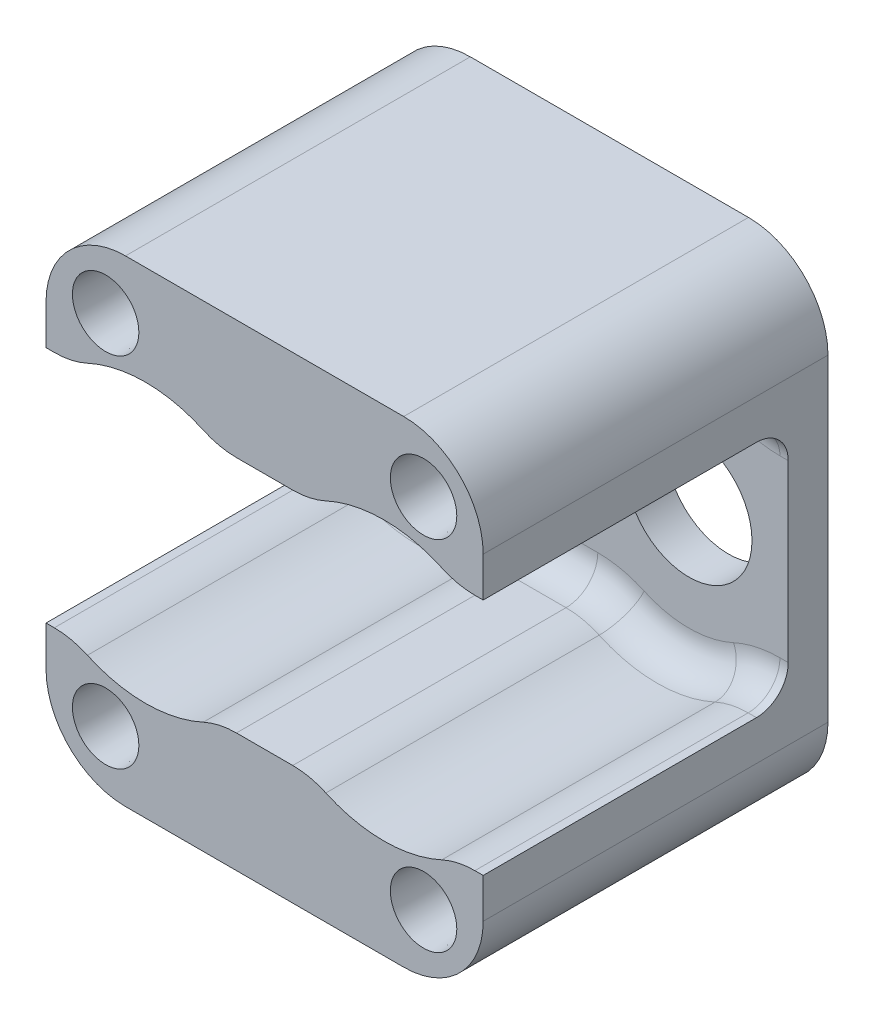
SolidWorks part; units mm, degrees
material "PET"
ref_plane "Front Plane" through (0, 0, 0) normal (0, 0, 1) x (1, 0, 0)
ref_plane "Top Plane" through (0, 0, 0) normal (0, 1, 0) x (1, 0, 0)
ref_plane "Right Plane" through (0, 0, 0) normal (1, 0, 0) x (0, 0, -1)
sketch "Sketch1" plane through (0, 0, 0) normal (0, 0, 1) x (1, 0, 0)
  line L0 (-19.05, 0) -> (0, 0) construction
  line L2 (7.9375, -19.05) -> (-26.9875, -19.05)
  line L3 (7.9375, -19.05) -> (7.9375, 19.05)
  line L4 (7.9375, 19.05) -> (-26.9875, 19.05)
  line L5 (-26.9875, -19.05) -> (-26.9875, 19.05)
  line L6 (7.9375, -19.05) -> (-26.9875, 19.05) construction
  line L7 (7.9375, 19.05) -> (-26.9875, -19.05) construction
  point P4 (-9.525, 0)
  dimension "D1" = 34.925
  dimension "D2" = 38.1
extrude "Boss-Extrude1" add sketch "Sketch1" along normal blind 3.175
sketch "Sketch2" plane through (0, 0, 3.175) normal (0, 0, 1) x (1, 0, 0)
  line L0 (7.9375, -19.05) -> (7.9375, 19.05) construction
  line L1 (-26.9875, 19.05) -> (7.9375, 19.05)
  line L2 (-26.9875, 19.05) -> (-26.9875, 9.525)
  line L3 (-26.9875, 9.525) -> (7.9375, 9.525)
  line L4 (7.9375, 19.05) -> (7.9375, 9.525)
  dimension "D1" = 9.525
extrude "Boss-Extrude2" add sketch "Sketch2" along normal up to surface (24.3713 mm away)
sketch "Sketch3" plane through (0, 0, 19.6088) normal (0, 0, 1) x (1, 0, 0)
  circle A0 centre (-19.05, 0) radius 11.1125
  circle A1 centre (0, 0) radius 11.1125
  dimension "D1" = 22.225
extrude "Cut-Extrude1" cut sketch "Sketch3" against normal up to surface (16.4338 mm away) and the other way through all contours A1 A0 | A0 A1 | A0 A1 region at (-9.525, 0, 19.6088) region at (0.6449, 0, 19.6088) region at (-19.6949, 0, 19.6088) up to face at (-13.8906, -4.7625, 3.175)
mirror "Mirror1" about plane through (0, 0, 0) normal (0, 1, 0) of "Cut-Extrude1", "Boss-Extrude2"
fillet "Fillet1" radius 6.35 12 edges at (7.9375, 19.05, 13.7732) (-26.9875, 19.05, 13.7732) (5.7238, 9.525, 15.3607) (-5.7238, 9.525, 15.3607) (-13.3262, 9.525, 15.3607) (-24.7738, 9.525, 15.3607) (7.9375, -19.05, 13.7732) (-26.9875, -19.05, 13.7732) (5.7238, -9.525, 15.3607) (-5.7238, -9.525, 15.3607) (-13.3262, -9.525, 15.3607) (-24.7738, -9.525, 15.3607)
fillet "Fillet2" radius 2.54 18 edges at (5.921, 9.671, 3.175) (0, 11.1125, 3.175) (-5.921, 9.671, 3.175) (-13.129, 9.671, 3.175) (-19.05, 11.1125, 3.175) (-24.971, 9.671, 3.175) (7.6062, -9.525, 3.175) (5.921, -9.671, 3.175) (0, -11.1125, 3.175) (-5.921, -9.671, 3.175) (-9.525, -9.525, 3.175) (-13.129, -9.671, 3.175) (-19.05, -11.1125, 3.175) (-24.971, -9.671, 3.175) (-26.6562, -9.525, 3.175)
sketch "Sketch4" plane through (0, 0, 3.175) normal (0, 0, 1) x (1, 0, 0)
  line L0 (-10.9857, 8.0643) -> (-27.1143, -8.0643) construction
  line L2 (-26.2611, -8.9174) -> (-27.9674, -7.2111) construction
  circle A0 centre (-19.05, 0) radius 4.9022
  point P8 (-19.05, 0)
  point P10 (-19.05, 0)
  dimension "D1" = 9.8044
extrude "Cut-Extrude2" cut sketch "Sketch4" against normal through all
hole_wizard "3/8 Clearance Hole1" positions "Sketch6" profile "Sketch5" hole size "3/8" standard "ANSI Inch" end condition through all
sketch "Sketch6" plane through (0, 0, 3.175) normal (0, 0, 1) x (1, 0, 0)
  point P0 (0, 0)
sketch "Sketch5" plane through (0, 0, 3.175) normal (1, 0, 0) x (0, -1, 0)
  line L0 (0, 0) -> (0, 3.175)
  line L1 (0, 3.175) -> (5.0419, 3.175)
  line L2 (5.0419, 3.175) -> (5.0419, 0)
  line L5 (5.0419, 0) -> (0, 0)
  line L11 (0, -6.35) -> (0, 107.95) construction
  dimension "Thru Hole Dia." = 10.0838
  dimension "Thru Hole Depth" = 3.175
hole_wizard "#6 Clearance Hole1" positions "Sketch8" profile "Sketch7" hole size "#6" standard "ANSI Inch" end condition through all
sketch "Sketch8" plane through (0, 0, 0) normal (0, 0, -1) x (-1, 0, 0)
  line L0 (-7.9375, -12.7) -> (-7.9375, 12.7) construction
  line L1 (-1.5875, 19.05) -> (20.6375, 19.05) construction
  line L2 (9.525, 19.05) -> (9.525, 0) construction
  line L3 (9.525, 0) -> (26.9875, 0) construction
  line L4 (26.9875, 12.7) -> (26.9875, -12.7) construction
  point P0 (-3.175, 14.2875)
  point P21 (22.225, 14.2875)
  point P23 (22.225, -14.2875)
  point P24 (-3.175, -14.2875)
  dimension "D1" = 4.7625
  dimension "D2" = 4.7625
sketch "Sketch7" plane through (3.175, 14.2875, 0) normal (1, 0, 0) x (0, 1, 0)
  line L0 (0, 0) -> (0, 27.5463)
  line L1 (0, 27.5463) -> (2.1526, 27.5463)
  line L2 (2.1526, 27.5463) -> (2.1526, 0)
  line L5 (2.1526, 0) -> (0, 0)
  line L11 (0, -6.35) -> (0, 107.95) construction
  dimension "Thru Hole Dia." = 4.3053
  dimension "Thru Hole Depth" = 27.5463
hole_wizard "Hole1" positions "Sketch10" profile "Sketch9" legacy
sketch "Sketch10" plane through (0, 0, 27.5463) normal (0, 0, 1) x (1, 0, 0)
  point P0 (-22.225, 14.2875)
  point P3 (3.175, 14.2875)
  point P6 (-22.225, -14.2875)
  point P9 (3.175, -14.2875)
sketch "Sketch9" plane through (-22.225, 14.2875, 27.5463) normal (1, 0, 0) x (0, -1, 0)
  line L0 (0, 0) -> (0, 3.81)
  line L1 (0, 3.81) -> (2.5273, 3.81)
  line L2 (2.5273, 3.81) -> (2.6543, 0)
  line L3 (2.6543, 0) -> (0, 0)
  line L4 (0, 110) -> (0, -10) construction
  dimension "Minor Diameter" = 5.0546
  dimension "Depth" = 3.81
  dimension "Major Diameter" = 5.3086
sketch "Sketch11" plane through (0, 0, 0) normal (0, 0, -1) x (-1, 0, 0)
  circle A0 centre (23.8252, -8.2709) radius 1.5875
  dimension "D1" = 3.175
extrude "Cut-Extrude3" cut sketch "Sketch11" against normal up to next
hole_wizard "Hole2" positions "Sketch13" profile "Sketch12" legacy
sketch "Sketch13" plane through (0, 0, 0) normal (0, 0, -1) x (-1, 0, 0)
  point P0 (22.225, 14.2875)
sketch "Sketch12" plane through (-22.225, 14.2875, 0) normal (1, 0, 0) x (0, 1, 0)
  line L0 (0, 0) -> (0, 3.81)
  line L1 (0, 3.81) -> (2.5273, 3.81)
  line L2 (2.5273, 3.81) -> (2.6543, 0)
  line L3 (2.6543, 0) -> (0, 0)
  line L4 (0, 110) -> (0, -10) construction
  dimension "Minor Diameter" = 5.0546
  dimension "Depth" = 3.81
  dimension "Major Diameter" = 5.3086
